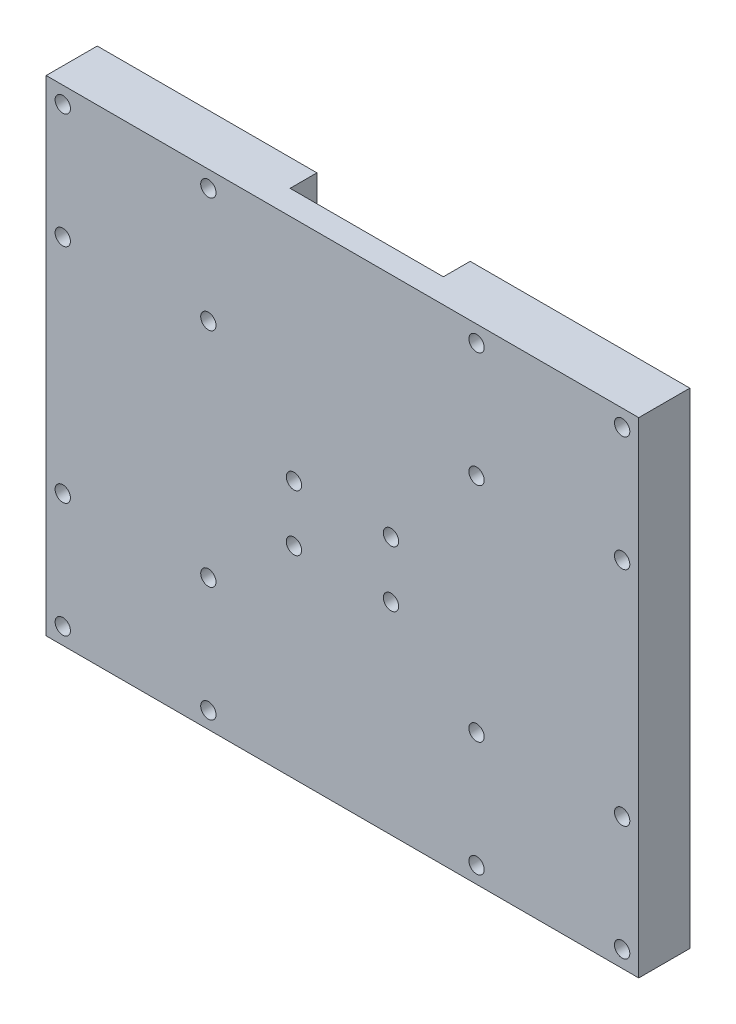
SolidWorks part; units mm, degrees
ref_plane "Piano frontale" through (0, 0, 0) normal (0, 0, 1) x (1, 0, 0)
ref_plane "Piano superiore" through (0, 0, 0) normal (0, 1, 0) x (1, 0, 0)
ref_plane "Piano destro" through (0, 0, 0) normal (1, 0, 0) x (0, 0, -1)
sketch "Schizzo1" plane through (0, 0, 0) normal (0, 0, 1) x (1, 0, 0)
  line L1 (116, -95) -> (-116, -95)
  line L2 (116, -95) -> (116, 95)
  line L3 (116, 95) -> (-116, 95)
  line L4 (-116, -95) -> (-116, 95)
  line L5 (116, -95) -> (-116, 95) construction
  line L6 (116, 95) -> (-116, -95) construction
  point P0 (0, 0)
  dimension "D1" = 232
  dimension "D2" = 190
extrude "Estrusione-Estrusione1" add sketch "Schizzo1" along normal blind 20
sketch "Schizzo3" plane through (0, 0, 20) normal (0, 0, 1) x (1, 0, 0)
  circle A8 centre (19, 6) radius 3
  circle A9 centre (-19, 6) radius 3
  circle A10 centre (-19, -16) radius 3
  circle A11 centre (19, -16) radius 3
  circle A14 centre (-109.5, 88.5) radius 3
  circle A15 centre (-52.5, 88.5) radius 3
  circle A18 centre (-109.5, 43.5) radius 3
  circle A19 centre (-52.5, 43.5) radius 3
  circle A24 centre (-109.5, -88.5) radius 3
  circle A25 centre (-109.5, -43.5) radius 3
  circle A26 centre (-52.5, -88.5) radius 3
  circle A27 centre (-52.5, -43.5) radius 3
extrude "Taglio-Estrusione1" cut sketch "Schizzo3" against normal through all
sketch "Schizzo4" plane through (0, 95, 0) normal (0, 1, 0) x (1, 0, 0)
  line L0 (116, 0) -> (-116, 0) construction
  line L1 (30, 0) -> (-30, 0)
  line L2 (30, 0) -> (30, -10.5)
  line L3 (30, -10.5) -> (-30, -10.5)
  line L4 (-30, 0) -> (-30, -10.5)
  dimension "D1" = 10.5
extrude "Taglio-Estrusione2" cut sketch "Schizzo4" against normal through all
mirror "Specchia1" about plane through (0, 0, 0) normal (1, 0, 0) of "Taglio-Estrusione1"
